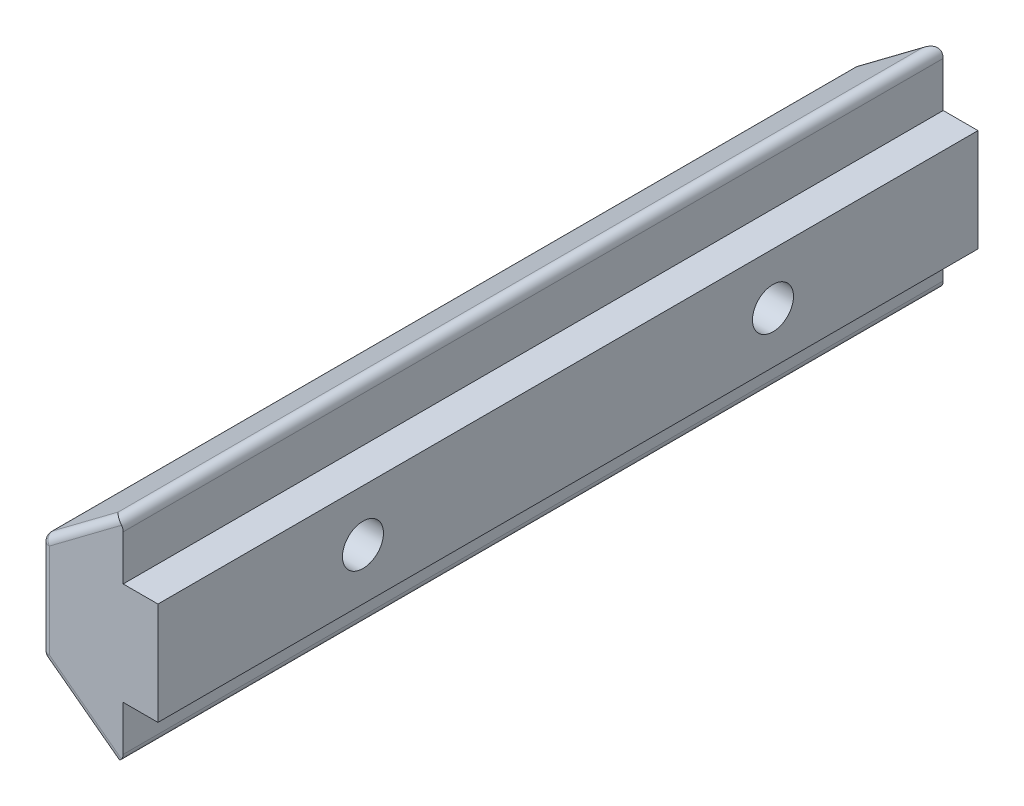
SolidWorks part; units mm, degrees
ref_plane "Plan de face" through (0, 0, 0) normal (0, 0, 1) x (1, 0, 0)
ref_plane "Plan de dessus" through (0, 0, 0) normal (0, 1, 0) x (1, 0, 0)
ref_plane "Plan de droite" through (0, 0, 0) normal (1, 0, 0) x (0, 0, -1)
sketch "ProfileRainureEsquisse" plane through (0, 0, 0) normal (0, 0, 1) x (1, 0, 0)
  line L0 (0, 0) -> (0, 5)
  line L1 (0, 5) -> (4, 8)
  line L2 (0, 0) -> (4, -3)
  line L3 (4, 8) -> (4, 5)
  line L4 (4, 5) -> (5.6958, 5)
  line L5 (5.6958, 5) -> (5.6958, 0)
  line L6 (5.6958, 0) -> (4, 0)
  line L7 (4, 0) -> (4, -3)
  dimension "D1" = 4
  dimension "D2" = 5.6958
  dimension "D3" = 5
  dimension "D4" = 8
extrude "Boss.-Extru.1" add sketch "ProfileRainureEsquisse" along normal blind 40
fillet "Congé8" radius 0.4 10 edges at (4, 8, 20) (2, 6.5, 40) (2, 6.5, 0) (0, 5, 20) (0, 2.5, 40) (0, 2.5, 0) (0, 0, 20) (2, -1.5, 40) (4, -3, 20) (2, -1.5, 0)
sketch "Esquisse1" plane through (5.6958, 0, 0) normal (1, 0, 0) x (0, 0, -1)
  line L0 (-40, 0) -> (-40, 5) construction
  circle A0 centre (-30, 2.5) radius 1
  point P2 (-40, 2.5)
  point P7 (-40, 2.5)
  point P10 (-40, 2.5)
  dimension "D1" = 2
  dimension "D2" = 10
extrude "Enlèv. mat.-Extru.1" cut sketch "Esquisse1" against normal through all
pattern_linear "Répétition linéaire2" count 2 spacing 20 along (0, 0, -1) of "Enlèv. mat.-Extru.1"
